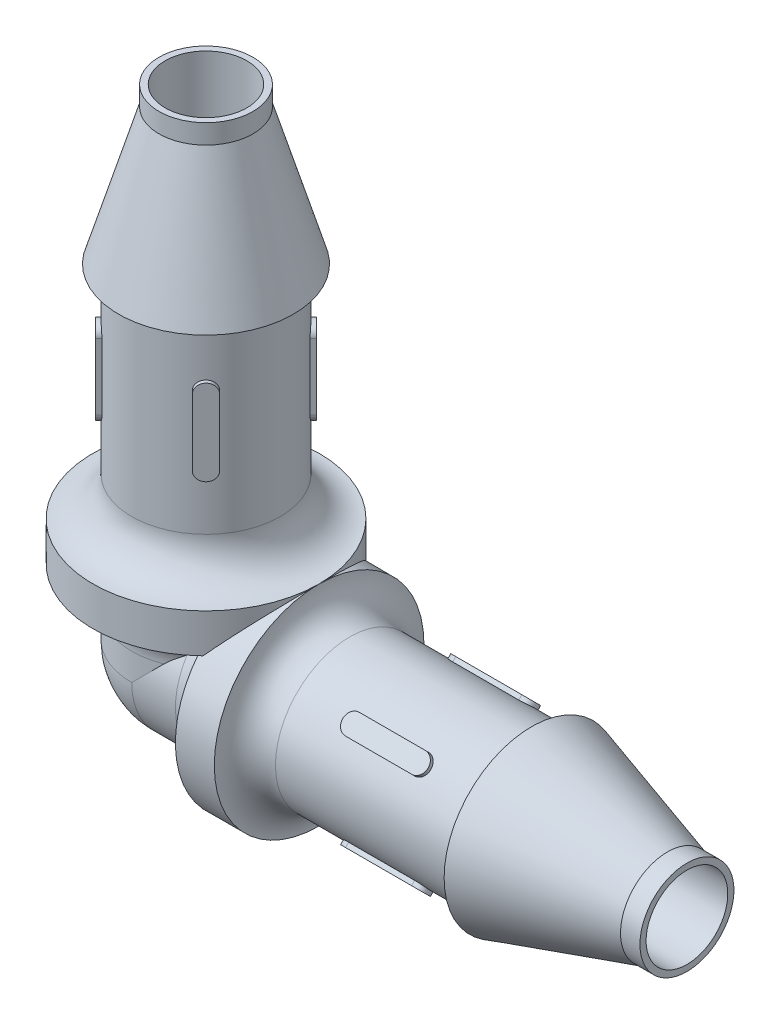
SolidWorks part; units mm, degrees
ref_plane "Front Plane" through (0, 0, 0) normal (0, 0, 1) x (1, 0, 0)
ref_plane "Top Plane" through (0, 0, 0) normal (0, 1, 0) x (1, 0, 0)
ref_plane "Right Plane" through (0, 0, 0) normal (1, 0, 0) x (0, 0, -1)
sketch "Sketch1" plane through (0, 0, 0) normal (0, 0, 1) x (1, 0, 0)
  line L0 (0, 0) -> (17.338, 0) construction
  line L1 (17.338, 1.4732) -> (17.338, -1.4732) construction
  line L2 (17.338, 3.1496) -> (17.338, -3.1496) construction
  line L3 (17.338, 2.3812) -> (17.338, -2.3813) construction
  line L4 (0, 0) -> (0, 2.6772) construction
  line L5 (0, 2.6772) -> (-2.6772, 2.6772) construction
  line L6 (0, 0) -> (0, 17.338) construction
  line L7 (0, 0) -> (0, -2.6772) construction
  point P6 (17.338, 0)
  point P8 (17.338, 0)
  point P11 (17.338, 0)
  dimension "D2" = 2.6772
  dimension "A" = 2.9464
  dimension "B" = 6.2992
  dimension "For Tube ID" = 4.7625
  dimension "D1" = 5.3543
  dimension "C" = 20.0152
  dimension "D" = 20.0152
sketch "Sketch01" plane through (0, 0, 0) normal (0, 0, 1) x (1, 0, 0)
  line L0 (0, 0) -> (17.338, 0) construction
  line L1 (17.338, 1.4732) -> (17.338, 1.6942)
  line L2 (2.6772, -2.6772) -> (0, -2.6772) construction
  line L3 (11.7338, 3.1496) -> (11.7338, 2.6772)
  line L4 (11.7338, 2.6772) -> (4.0782, 2.6772)
  line L5 (17.338, 1.6942) -> (16.6375, 1.6942)
  line L6 (4.0782, 2.6772) -> (4.0782, 3.7795)
  line L7 (4.0782, 3.7795) -> (2.6772, 3.7795)
  line L8 (2.6772, 3.7795) -> (2.6772, 2.6772)
  line L9 (2.6772, 2.6772) -> (0, 2.6772)
  line L10 (17.338, 1.4732) -> (0, 1.4732)
  line L11 (0, 1.4732) -> (0, 2.6772)
  line L12 (11.7338, 3.1496) -> (17.338, 3.1496) construction
  line L13 (0, 0) -> (0, -2.6772) construction
  line L14 (16.6375, 1.6942) -> (11.7338, 3.1496)
  line L15 (4.0782, 17.338) -> (0, 17.338) construction
  line L16 (-2.6772, 3.7795) -> (-2.6772, 2.6772) construction
  line L17 (0, 0) -> (0, 17.338) construction
  dimension "D3" = 5.6043
  dimension "D8" = 0.7005
  dimension "D7" = 5.3543
  dimension "D2" = 2.6772
  dimension "D6" = 2.6772
revolve "Revolve1" add sketch "Sketch01" angle 360 about L0
sketch "Sketch2" plane through (0, 0, 0) normal (0, 0, 1) x (1, 0, 0)
  line L0 (11.7338, 2.6772) -> (4.0782, 2.6772) construction
  line L1 (4.0782, 2.6772) -> (4.0782, 3.7795) construction
  line L2 (5.1806, 2.6772) -> (4.0782, 2.6772)
  line L3 (4.0782, 2.6772) -> (4.0782, 3.7795)
  line L4 (2.6772, 3.7795) -> (2.6772, 2.6772) construction
  line L5 (2.6772, 2.6772) -> (0, 2.6772) construction
  line L6 (2.6772, 3.7795) -> (2.6772, 2.6772)
  line L7 (2.6772, 2.6772) -> (1.5748, 2.6772)
  arc A0 (4.0782, 3.7795) -> (5.1806, 2.6772) centre (5.1806, 3.7795) ccw
  arc A1 (2.6772, 3.7795) -> (1.5748, 2.6772) centre (1.5748, 3.7795) cw
revolve "Revolve2" add sketch "Sketch2" angle 360 about L0
ref_plane "Plane1" through (0, 0, 0) normal (0, 0.7071, 0.7071) x (-1, 0, 0)
sketch "Sketch3" plane through (0, 0, 0) normal (0, 0.7071, 0.7071) x (-1, 0, 0)
  line L0 (0, 0) -> (-17.338, 0) construction
  line L1 (-7.2663, 0.3503) -> (-9.6481, 0.3503)
  line L2 (-7.2663, 0.3503) -> (-7.2663, -0.3503) construction
  line L3 (-7.2663, -0.3503) -> (-9.6481, -0.3503)
  line L4 (-9.6481, 0.3503) -> (-9.6481, -0.3503) construction
  line L5 (-5.1806, 2.6772) -> (-5.1806, 3.7795) construction
  line L6 (-5.1806, 3.7795) -> (-11.7338, 3.7795) construction
  line L7 (-11.7338, 3.7795) -> (-11.7338, 2.6772) construction
  line L8 (-8.4572, 3.7795) -> (-8.4572, 0.3503) construction
  line L9 (-5.1806, 2.6772) -> (-6.916, 2.6772) construction
  line L10 (-6.916, 2.6772) -> (-6.916, 0) construction
  line L11 (-11.7338, 2.6772) -> (-9.9984, 2.6772) construction
  line L12 (-9.9984, 2.6772) -> (-9.9984, 0) construction
  line L13 (-5.1806, 2.6772) -> (-11.7338, 2.6772) construction
  line L14 (-3.3777, 3.7795) -> (-5.1806, 3.7795) construction
  line L15 (-2.6772, 3.7795) -> (-4.0782, 3.7795) construction
  arc A0 (-9.6481, 0.3503) -> (-9.6481, -0.3503) centre (-9.6481, 0) ccw
  arc A1 (-7.2663, 0.3503) -> (-7.2663, -0.3503) centre (-7.2663, 0) cw
  dimension "D1" = 0.7005
  dimension "D2" = 3.0823
extrude "Extrude1" add sketch "Sketch3" along normal mid plane 5.622
pattern_circular "CirPattern1" count 2 every 90 about axis through (0, 0, 0) along (1, 0, 0) of "Extrude1"
sketch "Sketch4" plane through (17.338, 0, 0) normal (1, 0, 0) x (0, 0, -1)
  circle A0 centre (0, 0) radius 1.4732 construction
  circle A1 centre (0, 0) radius 1.4732
extrude "Cut-Extrude1" cut sketch "Sketch4" against normal through all
sketch "Sketch5" plane through (0, 0, 0) normal (0, 0, 1) x (1, 0, 0)
  line L0 (0, 0) -> (0, 15.346) construction
  line L1 (1.4732, 17.338) -> (1.6942, 17.338)
  line L2 (1.6942, 17.338) -> (1.6942, 16.6375)
  line L3 (1.6942, 16.6375) -> (3.1496, 11.7338)
  line L4 (3.1496, 11.7338) -> (2.6772, 11.7338)
  line L5 (2.6772, 11.7338) -> (2.6772, 3.7795)
  line L6 (2.6772, 3.7795) -> (4.0782, 3.7795)
  line L7 (1.4732, 17.338) -> (1.4732, 0)
  line L8 (17.338, 1.4732) -> (17.338, 1.6942) construction
  line L9 (4.0782, 3.7795) -> (2.6772, 3.7795) construction
  line L10 (4.0782, 17.338) -> (0, 17.338) construction
  line L11 (2.6772, 0) -> (1.4732, 0)
  line L12 (0, 0) -> (17.338, 0) construction
  line L13 (17.338, 1.6942) -> (16.6375, 1.6942) construction
  line L14 (4.0782, 3.7795) -> (4.0782, 2.3785)
  line L15 (4.0782, 2.3785) -> (2.6772, 2.3785)
  line L16 (2.6772, 2.3785) -> (2.6772, 0)
  line L17 (0, 0) -> (17.338, 0) construction
  line L18 (-2.6772, 2.3785) -> (-2.6772, 0) construction
  line L19 (-2.6772, 3.7795) -> (-2.6772, 2.6772) construction
  line L20 (0, 0) -> (8.669, 0) construction
  dimension "D3" = 5.6043
  dimension "D2" = 6.2992
  dimension "D4" = 5.3543
revolve "Revolve3" add sketch "Sketch5" angle 360 about L0
sketch "Sketch10" plane through (0, 0, 0) normal (0, 0, 1) x (1, 0, 0)
  line L0 (4.0782, 3.7795) -> (2.6772, 3.7795) construction
  line L1 (2.6772, 11.7338) -> (2.6772, 3.7795) construction
  line L2 (4.0782, 3.7795) -> (2.6772, 3.7795)
  line L3 (2.6772, 5.1806) -> (2.6772, 3.7795)
  line L4 (2.6772, 2.3785) -> (2.6772, 0) construction
  line L5 (4.0782, 2.3785) -> (2.6772, 2.3785) construction
  line L6 (2.6772, 2.3785) -> (2.6772, 0.9774)
  line L7 (4.0782, 2.3785) -> (2.6772, 2.3785)
  arc A0 (4.0782, 3.7795) -> (2.6772, 5.1806) centre (4.0782, 5.1806) cw
  arc A1 (4.0782, 2.3785) -> (2.6772, 0.9774) centre (4.0782, 0.9774) ccw
revolve "Revolve4" add sketch "Sketch10" angle 360 about L0
sketch "Sketch11" plane through (0, 0, 0) normal (-1, 0, 0) x (0, 0, 1)
  circle A0 centre (0, 0) radius 1.4732 construction
  circle A1 centre (0, 0) radius 1.4732
extrude "Cut-Extrude2" cut sketch "Sketch11" against normal through all
sketch "Sketch12" plane through (0, 0, 0) normal (0, -1, 0) x (1, 0, 0)
  circle A0 centre (0, 0) radius 1.4732 construction
  circle A1 centre (0, 0) radius 1.4732
sketch "Sketch13" plane through (0, 0, 0) normal (0, -1, 0) x (1, 0, 0)
  line L0 (0, 0) -> (0, 2.0752) construction
  line L2 (0, 1.4732) -> (0, 2.6772)
  line L3 (0, -2.6772) -> (0, -1.4732)
  line L4 (0, 1.4732) -> (0, 2.6772)
  line L5 (0, -2.6772) -> (0, -1.4732)
  arc A2 (0, 2.6772) -> (0, -2.6772) centre (0, 0) ccw
  arc A3 (0, 1.4732) -> (0, -1.4732) centre (0, 0) ccw
  arc A4 (0, 2.6772) -> (0, -2.6772) centre (0, 0) ccw
  arc A5 (0, 1.4732) -> (0, -1.4732) centre (0, 0) ccw
  dimension "D1" = 0
revolve "Revolve5" add sketch "Sketch13" angle 90 about L0
ref_plane "Plane2" through (0, 0, 0) normal (-0.7071, 0, 0.7071) x (0.7071, 0, 0.7071)
sketch "Sketch9" plane through (0, 0, 0) normal (-0.7071, 0, 0.7071) x (0.7071, 0, 0.7071)
  line L0 (0, 0) -> (0, 15.346) construction
  line L1 (-0.3503, 9.6481) -> (0.3503, 9.6481) construction
  line L2 (-0.3503, 9.6481) -> (-0.3503, 7.2663)
  line L3 (-0.3503, 7.2663) -> (0.3503, 7.2663) construction
  line L4 (0.3503, 9.6481) -> (0.3503, 7.2663)
  line L5 (3.1496, 11.7338) -> (3.1496, 5.1806) construction
  line L6 (3.1496, 8.4572) -> (-0.3503, 8.4572) construction
  line L7 (2.6772, 5.1806) -> (-2.6772, 5.1806) construction
  line L8 (-3.1496, 11.7338) -> (3.1496, 11.7338) construction
  arc A0 (-0.3503, 9.6481) -> (0.3503, 9.6481) centre (0, 9.6481) cw
  arc A1 (-0.3503, 7.2663) -> (0.3503, 7.2663) centre (0, 7.2663) ccw
  dimension "D2" = 0.7005
extrude "Extrude2" add sketch "Sketch9" along normal mid plane 5.622
pattern_circular "CirPattern2" count 2 every 90 about axis through (0, 0, 0) along (0, 1, 0) of "Extrude2"
sketch "Sketch7" plane through (0, 0, 0) normal (0, 1, 0) x (1, 0, 0)
  circle A0 centre (0, 0) radius 1.4732 construction
  circle A1 centre (0, 0) radius 1.4732
extrude "Cut-Extrude4" cut sketch "Sketch7" along normal through all
ref_axis "Axis1" through (16.796, 0, 0) along (-1, 0, 0)
ref_axis "Axis2" through (0, 12.9213, 0) along (0, -1, 0)
ref_point "Point1"
ref_point "Point2"
equation "\"D1@Sketch01\"=\"A@Sketch1\"*1.15"
equation "\"D3@Sketch01\"=\"C@Sketch1\"*.28"
equation "\"D4@Sketch01\"=\"C@Sketch1\"*.070"
equation "\"D5@Sketch01\"=\"B@Sketch1\"*1.2"
equation "\"D8@Sketch01\" = \"D3@Sketch01\"/8"
equation "\"D1@Sketch3\" = \"D8@Sketch01\""
equation "\"D2@Sketch3\" = \"D3@Sketch01\"*.55"
equation "\"D1@Sketch5\"=\"A@Sketch1\""
equation "\"D2@Sketch5\"=\"B@Sketch1\""
equation "\"D3@Sketch5\" = \"D3@Sketch01\""
equation "\"D1@Sketch9\" = \"D2@Sketch3\""
equation "\"D2@Sketch9\" = \"D1@Sketch3\""
equation "\"D1@Extrude2\" = \"D1@Extrude1\""
equation "\"D2@Sketch01\"=\"D7@Sketch01\"/2"
equation "\"D1@Extrude1\" = \"D7@Sketch01\"*1.05"
equation "\"D4@Sketch5\" = \"D7@Sketch01\""
equation "\"D7@Sketch01\"=\"B@Sketch1\"*.85"
equation "\"D6@Sketch01\" = \"D2@Sketch01\""
equation "\"D1@Sketch1\"=\"B@Sketch1\"*.85"
equation "\"D2@Sketch1\"=\"D1@Sketch1\"/2"
